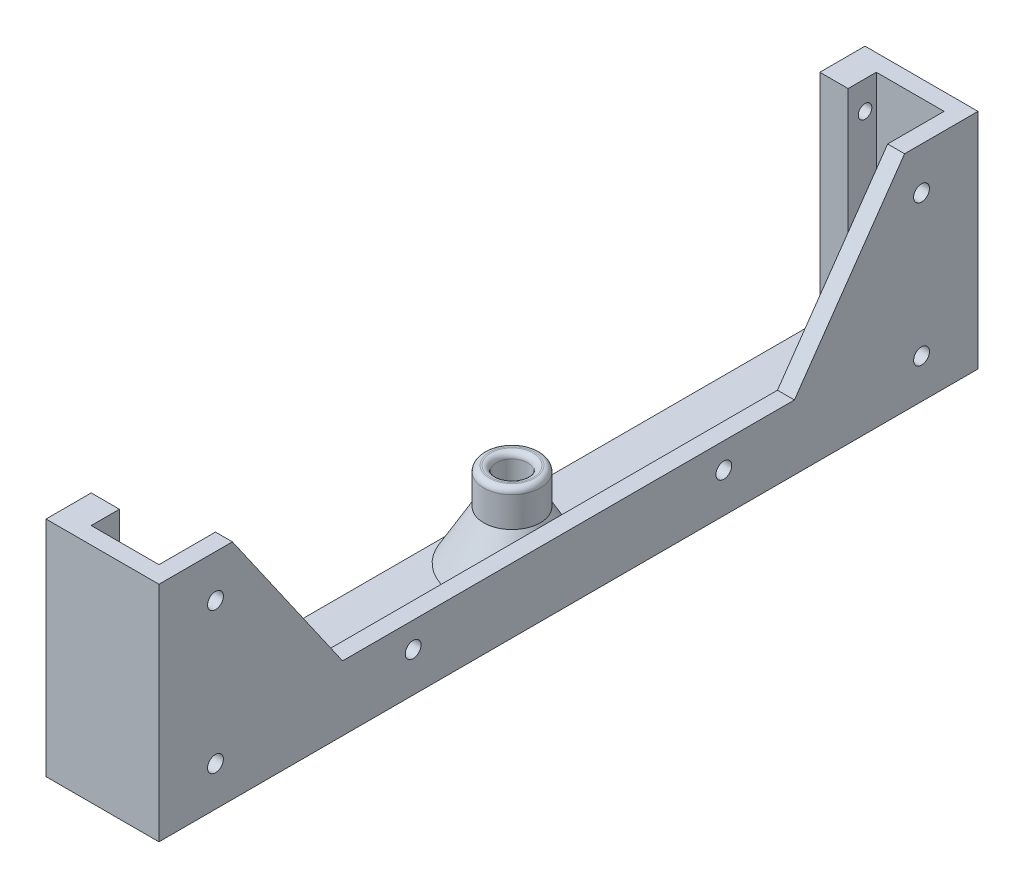
SolidWorks part; units mm, degrees
ref_plane "Спереди" through (0, 0, 0) normal (0, 0, 1) x (1, 0, 0)
ref_plane "Сверху" through (0, 0, 0) normal (0, 1, 0) x (1, 0, 0)
ref_plane "Справа" through (0, 0, 0) normal (1, 0, 0) x (0, 0, -1)
sketch "Эскиз1" plane through (0, 0, 0) normal (0, 1, 0) x (1, 0, 0)
  line L0 (0, 159.887) -> (0, 0) construction
  line L1 (0, 0) -> (281.7797, 0) construction
  line L2 (-60, -50) -> (-60, 50)
  line L3 (-20, -145) -> (20, -145)
  line L5 (-20, 145) -> (20, 145)
  line L6 (20, -145) -> (20, 145)
  line L7 (0, 145) -> (0, -145) construction
  line L8 (-435.8276, 0) -> (20, 0) construction
  line L9 (-60, 50) -> (-20, 145)
  line L10 (-60, -50) -> (-20, -145)
  point P10 (-60, 0)
  dimension "D1" = 290
  dimension "D2" = 40
  dimension "D3" = 100
  dimension "D4" = 80
extrude "Бобышка-Вытянуть1" add sketch "Эскиз1" along normal blind 4
sketch "Эскиз2" plane through (0, 0, 0) normal (0, 1, 0) x (1, 0, 0)
  line L1 (20, 145) -> (26, 145)
  line L2 (20, 145) -> (20, -145)
  line L3 (20, -145) -> (26, -145)
  line L4 (26, 145) -> (26, -145)
  dimension "D1" = 290
  dimension "D2" = 6
extrude "Бобышка-Вытянуть2" add sketch "Эскиз2" along normal blind 80
sketch "Эскиз17" plane through (0, 4, 0) normal (0, 1, 0) x (1, 0, 0)
  line L0 (-20, 145) -> (-60, 50)
  line L1 (-60, 50) -> (-60, -50)
  line L2 (-60, -50) -> (-20, -145)
  line L3 (-20, -145) -> (26, -145)
  line L4 (26, -145) -> (26, 145)
  line L5 (26, 145) -> (-20, 145)
extrude "Вытянуть-Тонкостенный1" add sketch "Эскиз17" along normal blind 96 thin thin type one direction reverse wall 6
sketch "Эскиз29" plane through (0, 100, 0) normal (0, 1, 0) x (1, 0, 0)
  line L1 (-60, 50) -> (-52, 50)
  line L2 (-60, 50) -> (-60, -50)
  line L3 (-60, -50) -> (-52, -50)
  line L4 (-52, 50) -> (-52, -50)
  dimension "D1" = 8
extrude "Бобышка-Вытянуть5" add sketch "Эскиз29" against normal blind 96
sketch "Эскиз20" plane through (-52, 0, 0) normal (1, 0, 0) x (0, 0, -1)
  line L0 (8.2314, 94.3113) -> (6.3873, 87.4288)
  line L1 (6.3, 52) -> (12.1612, 57.8612)
  line L10 (0, 0) -> (0, 100) construction
  line L12 (-48.7884, 52) -> (48.7884, 52) construction
  line L15 (-3, 95) -> (3, 95)
  line L16 (-3, 95) -> (-3, 87.8748)
  line L17 (-3, 87.8748) -> (3, 87.8748)
  line L18 (3, 95) -> (3, 87.8748)
  line L19 (0, 87.8748) -> (0, 95) construction
  line L20 (-3, 91.4374) -> (3, 91.4374) construction
  line L21 (8.2314, 94.3113) -> (14.027, 92.7584)
  line L22 (14.027, 92.7584) -> (12.1829, 85.8759)
  line L23 (6.3873, 87.4288) -> (12.1829, 85.8759)
  line L24 (18.9019, 90.7391) -> (15.3393, 84.5685)
  line L25 (18.9019, 90.7391) -> (24.0981, 87.7391)
  line L26 (24.0981, 87.7391) -> (20.5355, 81.5685)
  line L27 (15.3393, 84.5685) -> (20.5355, 81.5685)
  line L28 (28.2843, 84.5269) -> (23.246, 79.4886)
  line L29 (28.2843, 84.5269) -> (32.5269, 80.2843)
  line L30 (32.5269, 80.2843) -> (27.4886, 75.246)
  line L31 (23.246, 79.4886) -> (27.4886, 75.246)
  line L32 (35.7391, 76.0981) -> (29.5685, 72.5355)
  line L33 (35.7391, 76.0981) -> (38.7391, 70.9019)
  line L34 (38.7391, 70.9019) -> (32.5685, 67.3393)
  line L35 (29.5685, 72.5355) -> (32.5685, 67.3393)
  line L36 (40.7584, 66.027) -> (33.8759, 64.1829)
  line L37 (40.7584, 66.027) -> (42.3113, 60.2314)
  line L38 (42.3113, 60.2314) -> (35.4288, 58.3873)
  line L39 (33.8759, 64.1829) -> (35.4288, 58.3873)
  line L40 (43, 55) -> (35.8748, 55)
  line L41 (43, 55) -> (43, 49)
  line L42 (43, 49) -> (35.8748, 49)
  line L43 (35.8748, 55) -> (35.8748, 49)
  line L44 (42.3113, 43.7686) -> (35.4288, 45.6127)
  line L45 (42.3113, 43.7686) -> (40.7584, 37.973)
  line L46 (40.7584, 37.973) -> (33.8759, 39.8171)
  line L47 (35.4288, 45.6127) -> (33.8759, 39.8171)
  line L48 (38.7391, 33.0981) -> (32.5685, 36.6607)
  line L49 (38.7391, 33.0981) -> (35.7391, 27.9019)
  line L50 (35.7391, 27.9019) -> (29.5685, 31.4645)
  line L51 (32.5685, 36.6607) -> (29.5685, 31.4645)
  line L52 (32.5269, 23.7157) -> (27.4886, 28.754)
  line L53 (32.5269, 23.7157) -> (28.2843, 19.4731)
  line L54 (28.2843, 19.4731) -> (23.246, 24.5114)
  line L55 (27.4886, 28.754) -> (23.246, 24.5114)
  line L56 (24.0981, 16.2609) -> (20.5355, 22.4315)
  line L57 (24.0981, 16.2609) -> (18.9019, 13.2609)
  line L58 (18.9019, 13.2609) -> (15.3393, 19.4315)
  line L59 (20.5355, 22.4315) -> (15.3393, 19.4315)
  line L60 (14.027, 11.2416) -> (12.1829, 18.1241)
  line L61 (14.027, 11.2416) -> (8.2314, 9.6887)
  line L62 (8.2314, 9.6887) -> (6.3873, 16.5712)
  line L63 (12.1829, 18.1241) -> (6.3873, 16.5712)
  line L64 (3, 9) -> (3, 16.1252)
  line L65 (3, 9) -> (-3, 9)
  line L66 (-3, 9) -> (-3, 16.1252)
  line L67 (3, 16.1252) -> (-3, 16.1252)
  line L68 (-8.2314, 9.6887) -> (-6.3873, 16.5712)
  line L69 (-8.2314, 9.6887) -> (-14.027, 11.2416)
  line L70 (-14.027, 11.2416) -> (-12.1829, 18.1241)
  line L71 (-6.3873, 16.5712) -> (-12.1829, 18.1241)
  line L72 (-18.9019, 13.2609) -> (-15.3393, 19.4315)
  line L73 (-18.9019, 13.2609) -> (-24.0981, 16.2609)
  line L74 (-24.0981, 16.2609) -> (-20.5355, 22.4315)
  line L75 (-15.3393, 19.4315) -> (-20.5355, 22.4315)
  line L76 (-28.2843, 19.4731) -> (-23.246, 24.5114)
  line L77 (-28.2843, 19.4731) -> (-32.5269, 23.7157)
  line L78 (-32.5269, 23.7157) -> (-27.4886, 28.754)
  line L79 (-23.246, 24.5114) -> (-27.4886, 28.754)
  line L80 (-35.7391, 27.9019) -> (-29.5685, 31.4645)
  line L81 (-35.7391, 27.9019) -> (-38.7391, 33.0981)
  line L82 (-38.7391, 33.0981) -> (-32.5685, 36.6607)
  line L83 (-29.5685, 31.4645) -> (-32.5685, 36.6607)
  line L84 (-40.7584, 37.973) -> (-33.8759, 39.8171)
  line L85 (-40.7584, 37.973) -> (-42.3113, 43.7686)
  line L86 (-42.3113, 43.7686) -> (-35.4288, 45.6127)
  line L87 (-33.8759, 39.8171) -> (-35.4288, 45.6127)
  line L88 (-43, 49) -> (-35.8748, 49)
  line L89 (-43, 49) -> (-43, 55)
  line L90 (-43, 55) -> (-35.8748, 55)
  line L91 (-35.8748, 49) -> (-35.8748, 55)
  line L92 (-42.3113, 60.2314) -> (-35.4288, 58.3873)
  line L93 (-42.3113, 60.2314) -> (-40.7584, 66.027)
  line L94 (-40.7584, 66.027) -> (-33.8759, 64.1829)
  line L95 (-35.4288, 58.3873) -> (-33.8759, 64.1829)
  line L96 (-38.7391, 70.9019) -> (-32.5685, 67.3393)
  line L97 (-38.7391, 70.9019) -> (-35.7391, 76.0981)
  line L98 (-35.7391, 76.0981) -> (-29.5685, 72.5355)
  line L99 (-32.5685, 67.3393) -> (-29.5685, 72.5355)
  line L100 (-32.5269, 80.2843) -> (-27.4886, 75.246)
  line L101 (-32.5269, 80.2843) -> (-28.2843, 84.5269)
  line L102 (-28.2843, 84.5269) -> (-23.246, 79.4886)
  line L103 (-27.4886, 75.246) -> (-23.246, 79.4886)
  line L104 (-24.0981, 87.7391) -> (-20.5355, 81.5685)
  line L105 (-24.0981, 87.7391) -> (-18.9019, 90.7391)
  line L106 (-18.9019, 90.7391) -> (-15.3393, 84.5685)
  line L107 (-20.5355, 81.5685) -> (-15.3393, 84.5685)
  line L108 (-14.027, 92.7584) -> (-12.1829, 85.8759)
  line L109 (-14.027, 92.7584) -> (-8.2314, 94.3113)
  line L110 (-8.2314, 94.3113) -> (-6.3873, 87.4288)
  line L111 (-12.1829, 85.8759) -> (-6.3873, 87.4288)
  line L112 (6.276, 68.8704) -> (9.9019, 75.1506)
  line L113 (-3, 69.7482) -> (3, 69.7482)
  line L114 (-3, 69.7482) -> (-3, 77)
  line L115 (-3, 77) -> (3, 77)
  line L116 (3, 69.7482) -> (3, 77)
  line L117 (0, 77) -> (0, 69.7482) construction
  line L118 (-3, 73.3741) -> (3, 73.3741) construction
  line L119 (6.276, 68.8704) -> (11.4722, 65.8704)
  line L120 (11.4722, 65.8704) -> (15.0981, 72.1506)
  line L121 (9.9019, 75.1506) -> (15.0981, 72.1506)
  line L122 (13.8704, 63.4722) -> (20.1506, 67.0981)
  line L123 (13.8704, 63.4722) -> (16.8704, 58.276)
  line L124 (16.8704, 58.276) -> (23.1506, 61.9019)
  line L125 (20.1506, 67.0981) -> (23.1506, 61.9019)
  line L126 (17.7482, 55) -> (25, 55)
  line L127 (17.7482, 55) -> (17.7482, 49)
  line L128 (17.7482, 49) -> (25, 49)
  line L129 (25, 55) -> (25, 49)
  line L130 (16.8704, 45.724) -> (23.1506, 42.0981)
  line L131 (16.8704, 45.724) -> (13.8704, 40.5278)
  line L132 (13.8704, 40.5278) -> (20.1506, 36.9019)
  line L133 (23.1506, 42.0981) -> (20.1506, 36.9019)
  line L134 (11.4722, 38.1296) -> (15.0981, 31.8494)
  line L135 (11.4722, 38.1296) -> (6.276, 35.1296)
  line L136 (6.276, 35.1296) -> (9.9019, 28.8494)
  line L137 (15.0981, 31.8494) -> (9.9019, 28.8494)
  line L138 (3, 34.2518) -> (3, 27)
  line L139 (3, 34.2518) -> (-3, 34.2518)
  line L140 (-3, 34.2518) -> (-3, 27)
  line L141 (3, 27) -> (-3, 27)
  line L142 (-6.276, 35.1296) -> (-9.9019, 28.8494)
  line L143 (-6.276, 35.1296) -> (-11.4722, 38.1296)
  line L144 (-11.4722, 38.1296) -> (-15.0981, 31.8494)
  line L145 (-9.9019, 28.8494) -> (-15.0981, 31.8494)
  line L146 (-13.8704, 40.5278) -> (-20.1506, 36.9019)
  line L147 (-13.8704, 40.5278) -> (-16.8704, 45.724)
  line L148 (-16.8704, 45.724) -> (-23.1506, 42.0981)
  line L149 (-20.1506, 36.9019) -> (-23.1506, 42.0981)
  line L150 (-17.7482, 49) -> (-25, 49)
  line L151 (-17.7482, 49) -> (-17.7482, 55)
  line L152 (-17.7482, 55) -> (-25, 55)
  line L153 (-25, 49) -> (-25, 55)
  line L154 (-16.8704, 58.276) -> (-23.1506, 61.9019)
  line L155 (-16.8704, 58.276) -> (-13.8704, 63.4722)
  line L156 (-13.8704, 63.4722) -> (-20.1506, 67.0981)
  line L157 (-23.1506, 61.9019) -> (-20.1506, 67.0981)
  line L158 (-11.4722, 65.8704) -> (-15.0981, 72.1506)
  line L159 (-11.4722, 65.8704) -> (-6.276, 68.8704)
  line L160 (-6.276, 68.8704) -> (-9.9019, 75.1506)
  line L161 (-15.0981, 72.1506) -> (-9.9019, 75.1506)
  line L162 (6.3, 52) -> (12.1612, 46.1388)
  line L163 (-6.3, 52) -> (-12.1612, 57.8612)
  line L164 (-6.3, 52) -> (-12.1612, 46.1388)
  circle A0 centre (0, 52) radius 36 construction
  circle A1 centre (0, 52) radius 43 construction
  circle A3 centre (0, 52) radius 25 construction
  circle A4 centre (0, 52) radius 18 construction
  circle A5 centre (0, 52) radius 13.5 construction
  arc A6 (-12.1612, 57.8612) -> (12.1612, 57.8612) centre (0, 52) cw
  arc A7 (-12.1612, 46.1388) -> (12.1612, 46.1388) centre (0, 52) ccw
  point P15 (0, 91.4374)
  point P21 (0, 73.3741)
  point P112 (0, 52)
  point P163 (0, 52)
  dimension "D1" = 72
  dimension "D2" = 86
  dimension "D3" = 50
  dimension "D5" = 36
  dimension "D7" = 27
  dimension "D4" = 6
  dimension "D6" = 6
  dimension "D8" = 6.3
  dimension "D9" = 90
extrude "Вырез-Вытянуть7" cut sketch "Эскиз20" against normal blind 2
sketch "Эскиз16" plane through (26, 0, 0) normal (1, 0, 0) x (0, 0, -1)
  line L0 (0, 111.0778) -> (0, 40) construction
  line L1 (0, 40) -> (205.7417, 40) construction
  line L2 (-145, 0) -> (145, 0) construction
  line L3 (145, 100) -> (145, 0) construction
  line L4 (-162.396, 15) -> (215.9889, 15) construction
  circle A2 centre (125, 65) radius 2.8
  circle A3 centre (-125, 65) radius 2.8
  circle A4 centre (-125, 15) radius 2.8
  circle A5 centre (125, 15) radius 2.8
  circle A6 centre (55, 15) radius 2.8
  circle A7 centre (-55, 15) radius 2.8
  dimension "D2" = 5.6
  dimension "D3" = 25
  dimension "D4" = 20
  dimension "D5" = 90
  dimension "D1" = 40
extrude "Вырез-Вытянуть6" cut sketch "Эскиз16" against normal through all both and the other way through all
sketch "Эскиз21" plane through (-52, 0, 0) normal (1, 0, 0) x (0, 0, -1)
  line L0 (48.7884, 52) -> (-48.7884, 52) construction
  line L3 (0, 100) -> (0, 0) construction
  circle A0 centre (0, 52) radius 38.5 construction
  circle A1 centre (0, 90.5) radius 2
  circle A2 centre (9.9645, 89.1881) radius 2
  circle A3 centre (19.25, 85.342) radius 2
  circle A4 centre (27.2236, 79.2236) radius 2
  circle A5 centre (33.342, 71.25) radius 2
  circle A6 centre (37.1881, 61.9645) radius 2
  circle A7 centre (38.5, 52) radius 2
  circle A8 centre (37.1881, 42.0355) radius 2
  circle A9 centre (33.342, 32.75) radius 2
  circle A10 centre (27.2236, 24.7764) radius 2
  circle A11 centre (19.25, 18.658) radius 2
  circle A12 centre (9.9645, 14.8119) radius 2
  circle A13 centre (0, 13.5) radius 2
  circle A14 centre (-9.9645, 14.8119) radius 2
  circle A15 centre (-19.25, 18.658) radius 2
  circle A16 centre (-27.2236, 24.7764) radius 2
  circle A17 centre (-33.342, 32.75) radius 2
  circle A18 centre (-37.1881, 42.0355) radius 2
  circle A19 centre (-38.5, 52) radius 2
  circle A20 centre (-37.1881, 61.9645) radius 2
  circle A21 centre (-33.342, 71.25) radius 2
  circle A22 centre (-27.2236, 79.2236) radius 2
  circle A23 centre (-19.25, 85.342) radius 2
  circle A24 centre (-9.9645, 89.1881) radius 2
  circle A25 centre (0, 52) radius 21 construction
  circle A26 centre (0, 73) radius 2
  circle A27 centre (10.5, 70.1865) radius 2
  circle A28 centre (18.1865, 62.5) radius 2
  circle A29 centre (21, 52) radius 2
  circle A30 centre (18.1865, 41.5) radius 2
  circle A31 centre (10.5, 33.8135) radius 2
  circle A32 centre (0, 31) radius 2
  circle A33 centre (-10.5, 33.8135) radius 2
  circle A34 centre (-18.1865, 41.5) radius 2
  circle A35 centre (-21, 52) radius 2
  circle A36 centre (-18.1865, 62.5) radius 2
  circle A37 centre (-10.5, 70.1865) radius 2
  circle A38 centre (0, 52) radius 8.3 construction
  circle A39 centre (0, 60.3) radius 2
  circle A40 centre (7.188, 56.15) radius 2
  circle A41 centre (7.188, 47.85) radius 2
  circle A42 centre (0, 43.7) radius 2
  circle A43 centre (-7.188, 47.85) radius 2
  circle A44 centre (-7.188, 56.15) radius 2
  circle A45 centre (0, 52) radius 2
  point P64 (0, 52)
  point P90 (0, 52)
  point P104 (0, 52)
  dimension "D1" = 77
  dimension "D2" = 4
  dimension "D3" = 42
  dimension "D4" = 4
  dimension "D5" = 16.6
  dimension "D6" = 4
extrude "Отверстия под LED" cut sketch "Эскиз21" against normal blind 10
sketch "Эскиз22" plane through (0, 100, 0) normal (0, 1, 0) x (1, 0, 0)
  line L1 (26, 145) -> (-20, 145)
  line L2 (26, 145) -> (26, -145)
  line L3 (26, -145) -> (-20, -145)
  line L4 (-20, 145) -> (-20, -145)
extrude "Вырез-Вытянуть9" cut sketch "Эскиз22" against normal blind 20
fillet "Скругление3" radius 30 2 edges at (-60, 50, 50) (-60, 50, -50)
sketch "Эскиз23" plane through (-63.3172, 0, -26.6599) normal (0.9216, 0, 0.3881) x (0.3881, 0, -0.9216)
  line L0 (111.626, 100) -> (25.3247, 100) construction
  line L1 (40.9028, 100) -> (70.9028, 100)
  line L2 (40.9028, 100) -> (40.9028, 94)
  line L3 (40.9028, 94) -> (70.9028, 94)
  line L4 (70.9028, 100) -> (70.9028, 94)
  line L6 (25.9028, 4) -> (25.9028, 100) construction
  dimension "D1" = 30
  dimension "D2" = 6
  dimension "D3" = 15
extrude "Бобышка-Вытянуть3" add sketch "Эскиз23" along normal blind 10
sketch "Эскиз24" plane through (-63.3172, 0, 26.6599) normal (0.9216, 0, -0.3881) x (-0.3881, 0, -0.9216)
  line L0 (-25.3247, 100) -> (-111.626, 100) construction
  line L1 (-40.9028, 100) -> (-70.9028, 100)
  line L2 (-40.9028, 100) -> (-40.9028, 94)
  line L3 (-40.9028, 94) -> (-70.9028, 94)
  line L4 (-70.9028, 100) -> (-70.9028, 94)
  line L6 (-25.9028, 4) -> (-25.9028, 100) construction
  dimension "D1" = 30
  dimension "D2" = 6
  dimension "D3" = 15
extrude "Бобышка-Вытянуть4" add sketch "Эскиз24" along normal blind 10
chamfer "Фаска1" distance 10 angle 45 2 edges at (-41.6238, 94, -78.1819) (-41.6238, 94, 78.1819)
sketch "Эскиз27" plane through (26, 0, 0) normal (1, 0, 0) x (0, 0, -1)
  line L0 (-80, 24) -> (80, 24)
  line L1 (80, 24) -> (119, 80)
  line L2 (-145, 80) -> (145, 80) construction
  line L3 (119, 80) -> (-119, 80)
  line L4 (0, 118.8906) -> (0, 0) construction
  line L5 (-80, 24) -> (-119, 80)
  line L6 (-145, 0) -> (145, 0) construction
  line L7 (145, 80) -> (145, 0) construction
  point P10 (0, 80)
  point P11 (0, 24)
  dimension "D1" = 160
  dimension "D2" = 24
  dimension "D3" = 26
extrude "Вырез-Вытянуть10" cut sketch "Эскиз27" against normal blind 10
chamfer "Фаска2" distance 2 angle 45 24 edges at (-60, 71.25, 31.342) (-60, 61.9645, 35.1881) (-60, 52, 36.5) (-60, 42.0355, 35.1881) (-60, 32.75, 31.342) (-60, 24.7764, 25.2236) (-60, 18.658, 17.25) (-60, 14.8119, 7.9645) (-60, 13.5, -2) (-60, 14.8119, -11.9645) (-60, 18.658, -21.25) (-60, 24.7764, -29.2236) (-60, 32.75, -35.342) (-60, 42.0355, -39.1881) (-60, 52, -40.5) (-60, 61.9645, -39.1881) (-60, 71.25, -35.342) (-60, 79.2236, -29.2236) (-60, 85.342, -21.25) (-60, 89.1881, -11.9645) (-60, 90.5, -2) (-60, 79.2236, 25.2236) (-60, 85.342, 17.25) (-60, 89.1881, 7.9645)
sketch "Эскиз30" plane through (-52, 0, 0) normal (1, 0, 0) x (0, 0, -1)
  line L1 (-40, 12) -> (40, 12) construction
  line L2 (-40, 12) -> (-40, 92) construction
  line L3 (-40, 92) -> (40, 92) construction
  line L4 (40, 12) -> (40, 92) construction
  line L5 (0, 92) -> (0, 12) construction
  line L6 (-40, 52) -> (40, 52) construction
  circle A0 centre (-40, 92) radius 1.9
  circle A1 centre (40, 92) radius 1.9
  circle A2 centre (-40, 12) radius 1.9
  circle A3 centre (40, 12) radius 1.9
  point P0 (0, 52)
  dimension "D3" = 3.8
  dimension "D1" = 80
  dimension "D2" = 80
extrude "Вырез-Вытянуть11" cut sketch "Эскиз30" against normal blind 7
sketch "Эскиз32" plane through (0, 100, 0) normal (0, 1, 0) x (1, 0, 0)
  line L0 (-38, 139.8441) -> (-38, -154.1375) construction
  line L1 (-60, 43.9418) -> (-60, -43.9418) construction
  line L2 (0, 0) -> (-175.2904, 0) construction
  circle A0 centre (-38, 77.2619) radius 1.9
  circle A1 centre (-38, -77.2619) radius 1.9
  dimension "D2" = 77.2619
  dimension "D3" = 3.8
  dimension "D1" = 22
extrude "Вырез-Вытянуть13" cut sketch "Эскиз32" against normal blind 7
chamfer "Фаска3" distance 2 angle 45 7 edges at (-60, 47.85, 5.188) (-60, 43.7, -2) (-60, 47.85, -9.188) (-60, 56.15, -9.188) (-60, 52, -2) (-60, 56.15, 5.188) (-60, 60.3, -2)
chamfer "Фаска4" distance 2 angle 45 12 edges at (-60, 52, 19) (-60, 41.5, 16.1865) (-60, 33.8135, 8.5) (-60, 31, -2) (-60, 33.8135, -12.5) (-60, 41.5, -20.1865) (-60, 52, -23) (-60, 62.5, -20.1865) (-60, 70.1865, -12.5) (-60, 73, -2) (-60, 70.1865, 8.5) (-60, 62.5, 16.1865)
chamfer "Фаска5" distance 2 angle 45 6 edges at (20, 65, -127.8) (20, 15, -127.8) (20, 15, 122.2) (20, 65, 122.2) (20, 15, -57.8) (20, 15, 52.2)
sketch "Эскиз33" plane through (0, 4, 0) normal (0, 1, 0) x (1, 0, 0)
  line L0 (26, -80) -> (26, 80) construction
  circle A0 centre (6, 0) radius 10
  dimension "D1" = 20
  dimension "D2" = 20
extrude "Бобышка-Вытянуть6" add sketch "Эскиз33" along normal blind 30
chamfer "Фаска6" distance 10 angle 60 1 edges at (6, 4, -10) first distance on face at (6, 4, -10)
sketch "Эскиз34" plane through (0, 34, 0) normal (0, 1, 0) x (1, 0, 0)
  circle A0 centre (6, 0) radius 5.5
  dimension "D1" = 11
extrude "Вырез-Вытянуть14" cut sketch "Эскиз34" against normal through all both and the other way through all
fillet "Скругление4" radius 2 2 edges at (6, 34, 10) (6, 34, 5.5)
sketch "Эскиз35" plane through (0, 100, 0) normal (0, 1, 0) x (1, 0, 0)
  line L0 (26, 119) -> (26, 145) construction
  line L1 (-88.1388, -156.1498) -> (-14, -156.1498)
  line L2 (-88.1388, -156.1498) -> (-88.1388, 156.1498)
  line L3 (-88.1388, 156.1498) -> (-14, 156.1498)
  line L4 (-14, -156.1498) -> (-14, 156.1498)
  line L5 (-51.0694, 156.1498) -> (-51.0694, -156.1498) construction
  line L6 (-88.1388, 0) -> (-14, 0) construction
  point P0 (-51.0694, 0)
  dimension "D1" = 40
extrude "Вырез-Вытянуть15" cut sketch "Эскиз35" against normal through all both and the other way through all
sketch "Эскиз36" plane through (0, 4, 0) normal (0, 1, 0) x (1, 0, 0)
  line L0 (-49.1058, 0) -> (108.738, 0) construction
  line L1 (-14, 139) -> (-4, 139)
  line L2 (-14, 139) -> (-14, 129)
  line L3 (-14, 129) -> (-4, 129)
  line L4 (-4, 139) -> (-4, 129)
  line L5 (-14, -129) -> (-4, -129)
  line L6 (-4, -139) -> (-4, -129)
  line L7 (-14, -139) -> (-4, -139)
  line L8 (-14, -139) -> (-14, -129)
  dimension "D1" = 10
  dimension "D2" = 10
extrude "Бобышка-Вытянуть7" add sketch "Эскиз36" along normal up to surface (76 mm away) up to face at (10.6667, 80, -134.3333)
sketch "Эскиз37" plane through (-14, 0, 0) normal (-1, 0, 0) x (0, 0, 1)
  line L0 (-135, 80) -> (-135, -20.4461) construction
  line L1 (-145, 80) -> (-129, 80) construction
  line L2 (145, 0) -> (-145, 0) construction
  line L3 (0, -20.4461) -> (0, 97.6741) construction
  line L5 (-145, 0) -> (-145, 80) construction
  circle A0 centre (-135, 70) radius 2.4
  circle A1 centre (-135, 10) radius 2.4
  circle A2 centre (135, 10) radius 2.4
  circle A3 centre (135, 70) radius 2.4
  dimension "D1" = 4.8
  dimension "D3" = 10
  dimension "D2" = 10
  dimension "D4" = 10
extrude "Вырез-Вытянуть16" cut sketch "Эскиз37" against normal blind 20
chamfer "Фаска7" distance 1 angle 60 5 edges at (6, 0, 145) (26, 0, 0) (6, 0, -145) (6, 0, 5.5) (-14, 0, 0) first distance on face at (6, 40, 145) first distance on face at (26, 65, 127.8) first distance on face at (6, 40, -145) first distance on face at (6, 32, 5.5) first distance on face at (-14, 70, 132.6)
sketch "Эскиз38" plane through (0, 80, 0) normal (0, 1, 0) x (1, 0, 0)
  line L0 (20, 119) -> (26, 119) construction
  line L1 (-14, 145) -> (20, 145)
  line L2 (-14, 145) -> (-14, 119)
  line L3 (-14, 119) -> (20, 119)
  line L4 (20, 145) -> (20, 119)
  line L5 (20, 80) -> (20, 119) construction
  line L6 (-49.7032, 0) -> (69.8026, 0) construction
  line L7 (-14, -119) -> (20, -119)
  line L8 (20, -145) -> (20, -119)
  line L9 (-14, -145) -> (20, -145)
  line L10 (-14, -145) -> (-14, -119)
extrude "Вырез-Вытянуть17" [suppressed] cut sketch "Эскиз38" against normal up to surface (76 mm away)
